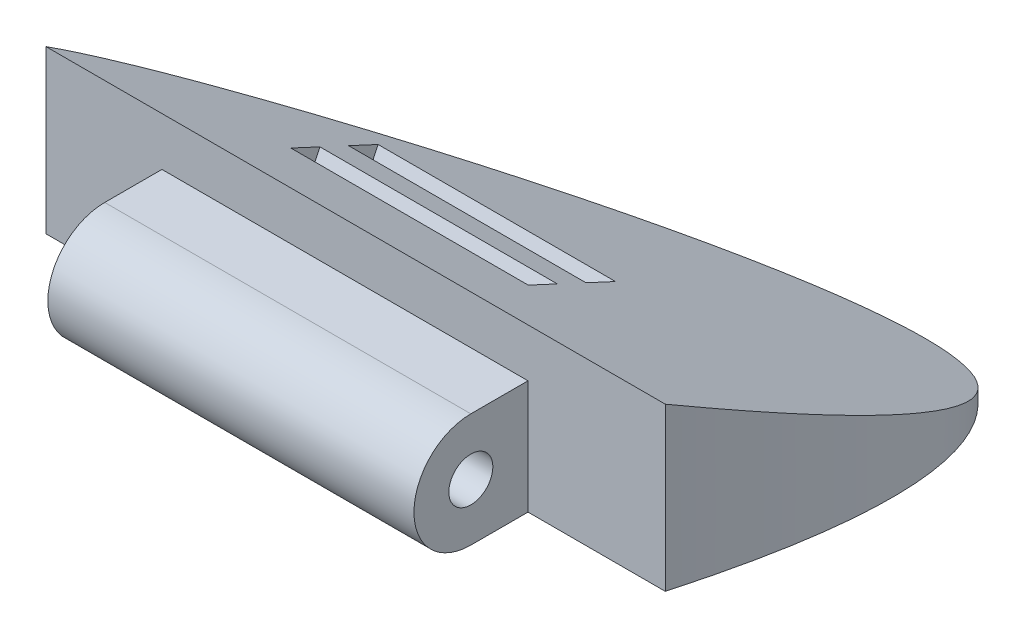
SolidWorks part; units mm, degrees
ref_plane "Front Plane" through (0, 0, 0) normal (0, 0, 1) x (1, 0, 0)
ref_plane "Top Plane" through (0, 0, 0) normal (0, 1, 0) x (1, 0, 0)
ref_plane "Right Plane" through (0, 0, 0) normal (1, 0, 0) x (0, 0, -1)
sketch "Sketch1" plane through (0, 0, 0) normal (0, 1, 0) x (1, 0, 0)
  line L0 (0, 0) -> (19.217, 0)
  line L1 (19.217, 0) -> (19.217, 6.0053)
  line L2 (19.217, 6.0053) -> (26.4233, 6.0053)
  line L3 (0, 0) -> (0, 6.0053)
  line L4 (0, 6.0053) -> (-6.0854, 6.0053)
  spline S0 degree 3 poles (26.4233, 6.0053) (36.5595, 42.6631) (-2.021, 14.397) (-6.0854, 6.0053) knots 0 0 0 0 1 1 1 1
extrude "Boss-Extrude1" add sketch "Sketch1" along normal blind 12.7
sketch "Sketch2" plane through (0, 12.7, 0) normal (0, 1, 0) x (1, 0, 0)
  line L1 (0, 6.0053) -> (19.217, 6.0053)
  line L2 (0, 6.0053) -> (0, 0)
  line L3 (0, 0) -> (19.217, 0)
  line L4 (19.217, 6.0053) -> (19.217, 0)
extrude "Cut-Extrude1" cut sketch "Sketch2" against normal blind 2.54
sketch "Sketch3" plane through (19.217, 0, 0) normal (1, 0, 0) x (0, 0, -1)
  line L0 (6.0053, 12.7) -> (6.0053, 0) construction
  line L1 (0, 10.16) -> (6.0053, 10.16)
  line L2 (0, 10.16) -> (0, 4.1896)
  line L3 (0, 4.1896) -> (6.0053, 4.1896)
  line L4 (6.0053, 10.16) -> (6.0053, 4.1896)
  line L5 (6.0053, 4.1896) -> (24.3276, 4.1896)
  line L6 (24.3276, 0) -> (24.3276, 12.7) construction
  line L7 (24.3276, 4.1896) -> (6.0053, 12.7)
  line L8 (6.0053, 12.7) -> (6.0053, 10.16)
  line L9 (6.0053, 12.7) -> (24.3276, 12.7)
  line L10 (24.3276, 12.7) -> (6.0053, 12.7) construction
  line L11 (24.3276, 12.7) -> (24.3276, 0)
  line L12 (24.3276, 0) -> (0, 0)
  line L13 (0, 0) -> (0, 4.1896)
  line L14 (6.0053, 10.16) -> (6.0053, 12.7)
  arc A0 (3.0026, 10.16) -> (3.0026, 4.1896) centre (3.0026, 7.1748) ccw
  circle A1 centre (3.0026, 7.1748) radius 1.1552
  line M8 (0, 10.16) -> (0, 0)
  line M9 (0, 0) -> (6.0053, 0)
  line M10 (6.0053, 0) -> (6.0053, 10.16)
extrude "Cut-Extrude2" cut sketch "Sketch3" against normal blind 26.924 and the other way blind 11.684 contours L11 L9 L7 | L12 L11 L5 M10 | L3 M8 M9 M10 | A0 L1 L3 M8 | A1 region at (19.217, 10.0932, -1.5013) region at (19.217, 2.0948, -3.0026) region at (19.217, 2.0948, -15.1665) region at (19.217, 9.8632, -18.2202) region at (19.217, 7.1748, -3.0026)
sketch "Sketch4" plane through (0, 12.7406, -5.9178) normal (0, 0.9069, -0.4213) x (1, 0, 0)
  line L0 (9.6085, -3.2844) -> (9.6085, 15.6114) construction
  line L2 (3.3779, 3.8349) -> (15.839, 3.8349)
  line L3 (15.839, 3.8349) -> (15.839, 8.8819)
  line L4 (15.839, 8.8819) -> (3.3779, 8.8819)
  line L5 (9.6085, 8.8819) -> (9.6085, 7.1756)
  line L6 (3.3779, 7.1756) -> (15.839, 7.1756)
  line L7 (9.6085, 3.8349) -> (9.6085, 5.5172)
  line L8 (3.3779, 5.5172) -> (15.839, 5.5172)
  line L9 (3.3779, 3.8349) -> (3.3779, 8.8819)
extrude "Cut-Extrude4" cut sketch "Sketch4" against normal blind 3.81 contours L9 L6 L5 L4 | L5 L6 L3 L4 | L8 L7 L2 L3 | L9 L2 L7 L8 region at (6.4932, 10.7708, -10.1587) region at (12.7237, 10.7708, -10.1587) region at (6.4932, 9.3584, -13.1994) region at (12.7237, 9.3584, -13.1994)
sketch "Sketch5" plane through (0, -2.3242, -5.0038) normal (0, 0.4213, 0.9069) x (1, 0, 0)
  line L1 (15.839, 14.0479) -> (2.7174, 14.0479)
  line L2 (15.839, 14.0479) -> (15.839, 10.1948)
  line L3 (15.839, 10.1948) -> (2.7174, 10.1948)
  line L4 (2.7174, 14.0479) -> (2.7174, 10.1948)
  line L5 (2.7174, 10.1948) -> (15.839, 10.1948)
  line L6 (2.7174, 10.1948) -> (2.7174, 12.1213)
  line L7 (2.7174, 12.1213) -> (15.839, 12.1213)
  line L8 (15.839, 10.1948) -> (15.839, 12.1213)
  line M2 (3.3779, 14.0479) -> (3.3779, 10.2379)
  line M3 (3.3779, 10.2379) -> (15.839, 10.2379)
  line M4 (15.839, 10.2379) -> (15.839, 14.0479)
extrude "Cut-Extrude5" cut sketch "Sketch5" against normal blind 2.54 contours L7 M2 M3 M4 region at (9.6085, 7.8151, -9.7133)
sketch "Sketch6" plane through (0, 4.1896, 0) normal (0, -1, 0) x (-1, 0, 0)
  line L0 (-9.6085, 0.0174) -> (-9.6085, 21.6986) construction
  line L2 (-9.6085, 8.3869) -> (-9.6085, 10.0736)
  line L3 (-3.171, 8.3869) -> (-16.046, 8.3869)
  line L4 (-9.6085, 8.3869) -> (-9.6085, 13.5102)
  line L5 (-3.171, 13.5102) -> (-16.046, 13.5102)
  line L6 (-16.046, 8.3869) -> (-16.046, 13.5102)
  line L7 (-3.171, 10.0736) -> (-16.046, 10.0736)
  line L8 (-9.6085, 13.5102) -> (-9.6085, 11.8529)
  line L9 (-3.171, 11.8529) -> (-16.046, 11.8529)
  line L10 (-3.171, 8.3869) -> (-3.171, 13.5102)
extrude "Cut-Extrude6" cut sketch "Sketch6" against normal blind 3.81 and the other way through all contours L3 L10 L7 L2 | L2 L7 L6 L3 | L9 L4 L5 L6 | L9 L10 L5 L4 region at (12.8272, 4.1896, -9.2303) region at (6.3897, 4.1896, -9.2303) region at (12.8272, 4.1896, -12.6815) region at (6.3897, 4.1896, -12.6815)
equation "\"0.15n\"=0.1"
